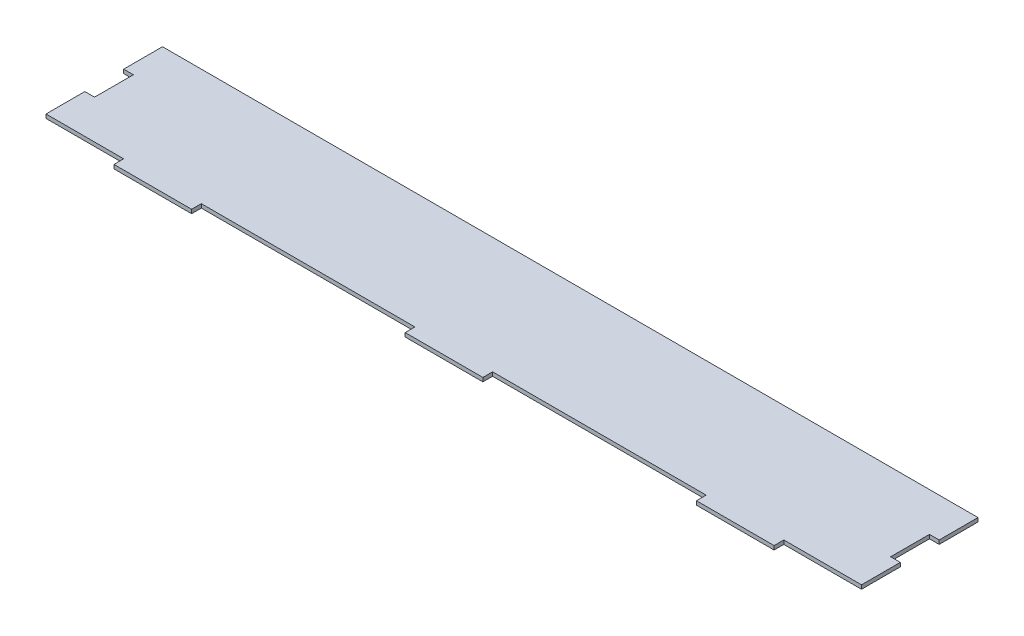
SolidWorks part; units mm, degrees
ref_plane "Front Plane" through (0, 0, 0) normal (0, 0, 1) x (1, 0, 0)
ref_plane "Top Plane" through (0, 0, 0) normal (0, 1, 0) x (1, 0, 0)
ref_plane "Right Plane" through (0, 0, 0) normal (1, 0, 0) x (0, 0, -1)
sketch "Sketch1" plane through (0, 0, 0) normal (0, 1, 0) x (1, 0, 0)
  line L0 (0, -25.4) -> (0, 0)
  line L1 (0, 0) -> (533.4, 0)
  line L2 (0, -50.8) -> (0, -76.2)
  line L3 (0, -76.2) -> (50.8, -76.2)
  line L4 (533.4, 0) -> (533.4, -25.4)
  line L5 (0, -25.4) -> (6.35, -25.4)
  line L6 (533.4, -50.8) -> (533.4, -76.2)
  line L7 (0, -50.8) -> (6.35, -50.8)
  line L8 (6.35, -25.4) -> (6.35, -50.8)
  line L9 (533.4, 0) -> (527.05, 0)
  line L10 (533.4, -25.4) -> (527.05, -25.4)
  line L11 (101.6, -76.2) -> (241.3, -76.2)
  line L12 (533.4, -50.8) -> (527.05, -50.8)
  line L13 (482.6, -76.2) -> (533.4, -76.2)
  line L14 (527.05, -25.4) -> (527.05, -50.8)
  line L15 (292.1, -76.2) -> (431.8, -76.2)
  line L16 (50.8, -76.2) -> (50.8, -82.55)
  line L17 (50.8, -82.55) -> (101.6, -82.55)
  line L18 (101.6, -76.2) -> (101.6, -82.55)
  line L20 (482.6, -76.2) -> (482.6, -82.55)
  line L21 (482.6, -82.55) -> (431.8, -82.55)
  line L22 (431.8, -76.2) -> (431.8, -82.55)
  line L24 (241.3, -76.2) -> (241.3, -82.55)
  line L25 (241.3, -82.55) -> (292.1, -82.55)
  line L26 (292.1, -76.2) -> (292.1, -82.55)
  dimension "D1" = 76.2
  dimension "D2" = 533.4
  dimension "D3" = 6.35
  dimension "D4" = 25.4
  dimension "D5" = 50.8
  dimension "D6" = 6.35
  dimension "D7" = 25.4
  dimension "D8" = 25.4
  dimension "D9" = 25.4
  dimension "D10" = 25.4
  dimension "D11" = 25.4
  dimension "D12" = 6.35
  dimension "D13" = 50.8
  dimension "D14" = 50.8
  dimension "D15" = 6.35
  dimension "D16" = 533.4
  dimension "D17" = 6.35
  dimension "D18" = 50.8
  dimension "D19" = 50.8
  dimension "D20" = 50.8
  dimension "D21" = 6.35
  dimension "D22" = 139.7
  dimension "D23" = 139.7
  dimension "D24" = 139.7
  dimension "D25" = 139.7
  dimension "D26" = 50.8
  dimension "D27" = 6.35
  dimension "D28" = 6.35
  dimension "D29" = 6.35
  dimension "D30" = 25.4
  dimension "D31" = 25.4
  dimension "D32" = 25.4
extrude "Boss-Extrude1" add sketch "Sketch1" along normal blind 2.54 contours L26 L15 L22 L21 L20 L13 L6 L12 L14 L10 L4 L1 L0 L5 L8 L7 L2 L3 L16 L17 L18 L11 L24 L25 region at (266.7, 0, 39.0674)
shell "Shell1" thickness 0.1016
